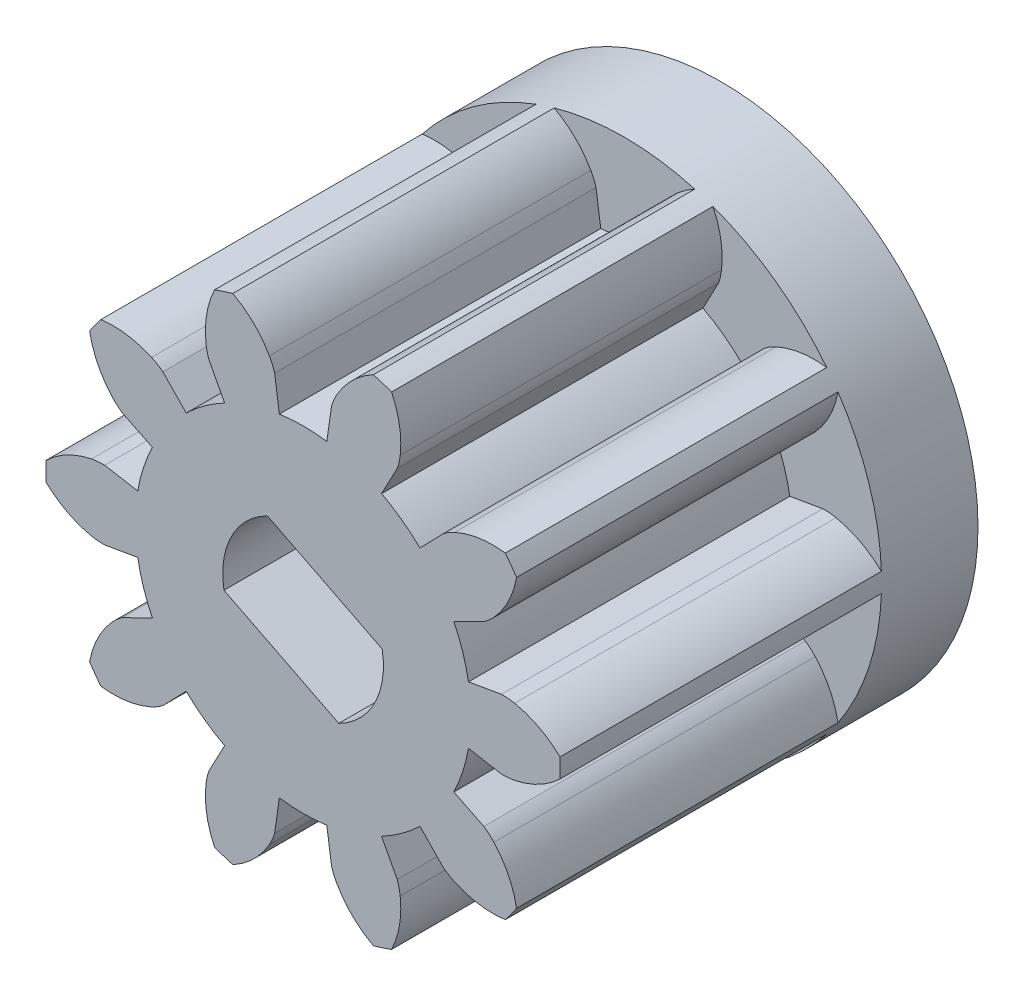
SolidWorks part; units mm, degrees
ref_plane "Plano frontal" through (0, 0, 0) normal (0, 0, 1) x (1, 0, 0)
ref_plane "Plano superior" through (0, 0, 0) normal (0, 1, 0) x (1, 0, 0)
ref_plane "Plano direito" through (0, 0, 0) normal (1, 0, 0) x (0, 0, -1)
sketch "Esboço1" plane through (0, 0, -24.3983) normal (0, 0, 1) x (1, 0, 0)
  line L0 (156.8059, -4.5413) -> (153.2345, -2.7399)
  line L1 (155.4549, -7.2198) -> (151.8834, -5.4184)
  arc A0 (156.8059, -4.5413) -> (155.4549, -7.2198) centre (154.3447, -4.9798) cw
  arc A2 (151.8834, -5.4184) -> (153.2345, -2.7399) centre (154.3447, -4.9798) cw
  circle A3 centre (154.3447, -4.9798) radius 8
  dimension "D1" = 16
extrude "Ressalto-extrusão1" add sketch "Esboço1" along normal up to surface (13 mm away)
sketch "Esboço4" plane through (0, 0, -11.3983) normal (0, 0, 1) x (1, 0, 0)
  line L0 (155.083, -10.1499) -> (155.2303, -11.1819)
  line L1 (154.3447, -4.9798) -> (154.3447, -12.9798) construction
  line L2 (153.6064, -10.1499) -> (153.459, -11.1819)
  circle A0 centre (154.3447, -4.9798) radius 5.2225 construction
  circle A1 centre (154.3447, -4.9798) radius 6.265 construction
  circle A2 centre (154.3447, -4.9798) radius 6.665 construction
  arc A4 (155.2303, -11.1819) -> (155.3917, -11.5621) centre (156.975, -10.6659) ccw
  arc A5 (155.3917, -11.5621) -> (156.532, -12.675) centre (157.8831, -10.1499) ccw
  arc A6 (153.459, -11.1819) -> (153.2977, -11.5621) centre (151.7143, -10.6659) cw
  arc A7 (153.2977, -11.5621) -> (152.1573, -12.675) centre (150.8062, -10.1499) cw
  arc A8 (155.083, -10.1499) -> (153.6064, -10.1499) centre (154.3447, -4.9798) cw
  arc A9 (156.532, -12.675) -> (152.1573, -12.675) centre (154.3447, -4.9798) cw
  circle A10 centre (154.3447, -4.9798) radius 8 construction
  point P4 (0, 0)
  point P5 (0, 0)
  point P15 (0, 0)
  point P16 (0, 0)
  point P17 (155.1567, -10.6659)
  point P18 (0, 0)
  point P19 (0, 0)
  point P29 (0, 0)
  dimension "D1" = 13.33
  dimension "D2" = 10.445
  dimension "D3" = 12.53
  dimension "D4" = 2.094
extrude "Corte-extrusão1" cut sketch "Esboço4" against normal blind 10
pattern_circular "PadrãoCircular1" count 10 over 360 about axis through (154.3447, -4.9798, -11.3983) along (0, 0, -1) of "Corte-extrusão1"
